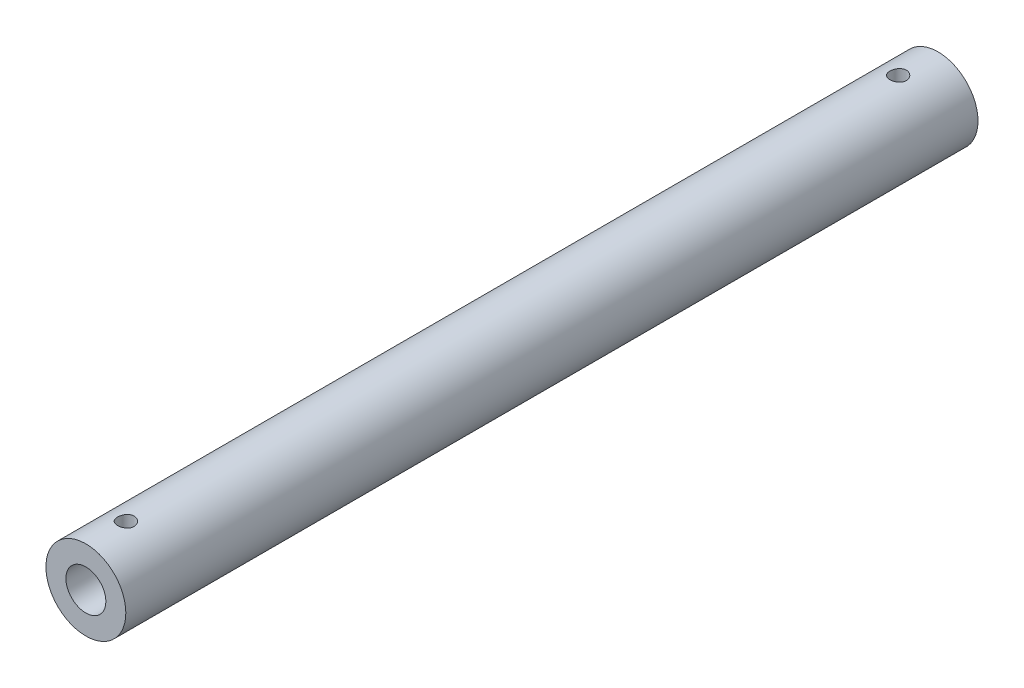
SolidWorks part; units mm, degrees
ref_plane "Front Plane" through (0, 0, 0) normal (0, 0, 1) x (1, 0, 0)
ref_plane "Top Plane" through (0, 0, 0) normal (0, 1, 0) x (1, 0, 0)
ref_plane "Right Plane" through (0, 0, 0) normal (1, 0, 0) x (0, 0, -1)
sketch "Sketch1" plane through (0, 0, 0) normal (0, 0, 1) x (1, 0, 0)
  circle A0 centre (0, 0) radius 15
  circle A1 centre (0, 0) radius 7.5
  dimension "D1" = 30
  dimension "D2" = 7.5
extrude "Boss-Extrude1" add sketch "Sketch1" along normal blind 160 and the other way blind 160
sketch "Sketch2" plane through (0, 0, 0) normal (0, 1, 0) x (1, 0, 0)
  line L0 (-15, -160) -> (15, -160) construction
  circle A0 centre (0, -145) radius 3.1
  dimension "D1" = 6.2
  dimension "D2" = 15
extrude "Cut-Extrude1" cut sketch "Sketch2" along normal through all
mirror "Mirror1" about plane through (0, 0, 0) normal (0, 0, 1) of "Cut-Extrude1"
